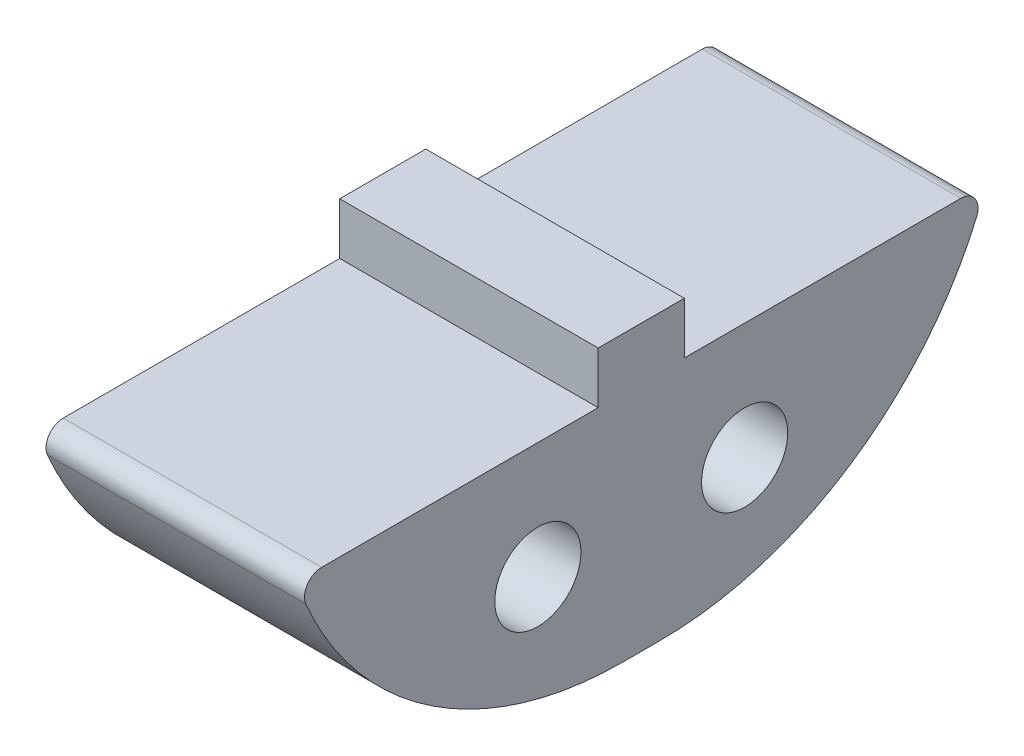
SolidWorks part; units mm, degrees
ref_plane "Front Plane" through (0, 0, 0) normal (0, 0, 1) x (1, 0, 0)
ref_plane "Top Plane" through (0, 0, 0) normal (0, 1, 0) x (1, 0, 0)
ref_plane "Right Plane" through (0, 0, 0) normal (1, 0, 0) x (0, 0, -1)
sketch "Sketch1" plane through (0, 0, 0) normal (0, 1, 0) x (1, 0, 0)
  line L1 (-15, -40) -> (15, -40)
  line L2 (-15, -40) -> (-15, 40)
  line L3 (-15, 40) -> (15, 40)
  line L4 (15, -40) -> (15, 40)
  line L5 (-15, -40) -> (15, 40) construction
  line L6 (-15, 40) -> (15, -40) construction
  point P0 (0, 0)
  dimension "D1" = 30
  dimension "D2" = 80
extrude "Boss-Extrude1" add sketch "Sketch1" along normal blind 27 contours L2 L3 L4 L1
sketch "Sketch2" plane through (15, 0, 0) normal (1, 0, 0) x (0, 0, -1)
  line L0 (-40, 13.5) -> (40, 13.5) construction
  line L1 (-40, 27) -> (-40, 0) construction
  line L2 (40, 27) -> (40, 0) construction
  line L3 (0, 0) -> (0, 27) construction
  line L4 (-40, 27) -> (40, 27) construction
  circle A0 centre (-12, 13.5) radius 5
  circle A1 centre (12, 13.5) radius 5
  dimension "D1" = 12
sketch "Sketch5" plane through (0, 27, 0) normal (0, 1, 0) x (1, 0, 0)
  line L2 (0, -40) -> (0, 40) construction
  line L3 (-15, -40) -> (15, -40) construction
  line L4 (-15, 40) -> (15, 40) construction
  line L5 (-15, 0) -> (15, 0) construction
  line L6 (-15, -40) -> (-15, 40) construction
  line L7 (15, -40) -> (15, 40) construction
  line L9 (-15, -5) -> (15, -5)
  line L10 (-15, -5) -> (-15, 5)
  line L11 (-15, 5) -> (15, 5)
  line L12 (15, -5) -> (15, 5)
  line L13 (-15, -5) -> (15, 5) construction
  line L14 (-15, 5) -> (15, -5) construction
  point P12 (0, 0)
  dimension "D1" = 10
extrude "Boss-Extrude2" add sketch "Sketch5" along normal blind 6
extrude "Cut-Extrude1" cut sketch "Sketch2" against normal blind 40 contours A0 | A1
fillet "Fillet5" radius 40 1 edges at (0, 0, -40)
fillet "Fillet6" radius 40 1 edges at (0, 0, 40)
fillet "Fillet7" radius 2 1 edges at (0, 27, -40)
fillet "Fillet8" radius 2 1 edges at (0, 27, 40)
sketch "Sketch6" plane through (15, 0, 0) normal (1, 0, 0) x (0, 0, -1)
  point P0 (-12, 13.5)
  point P1 (12, 13.5)
  dimension "D1" = 24
